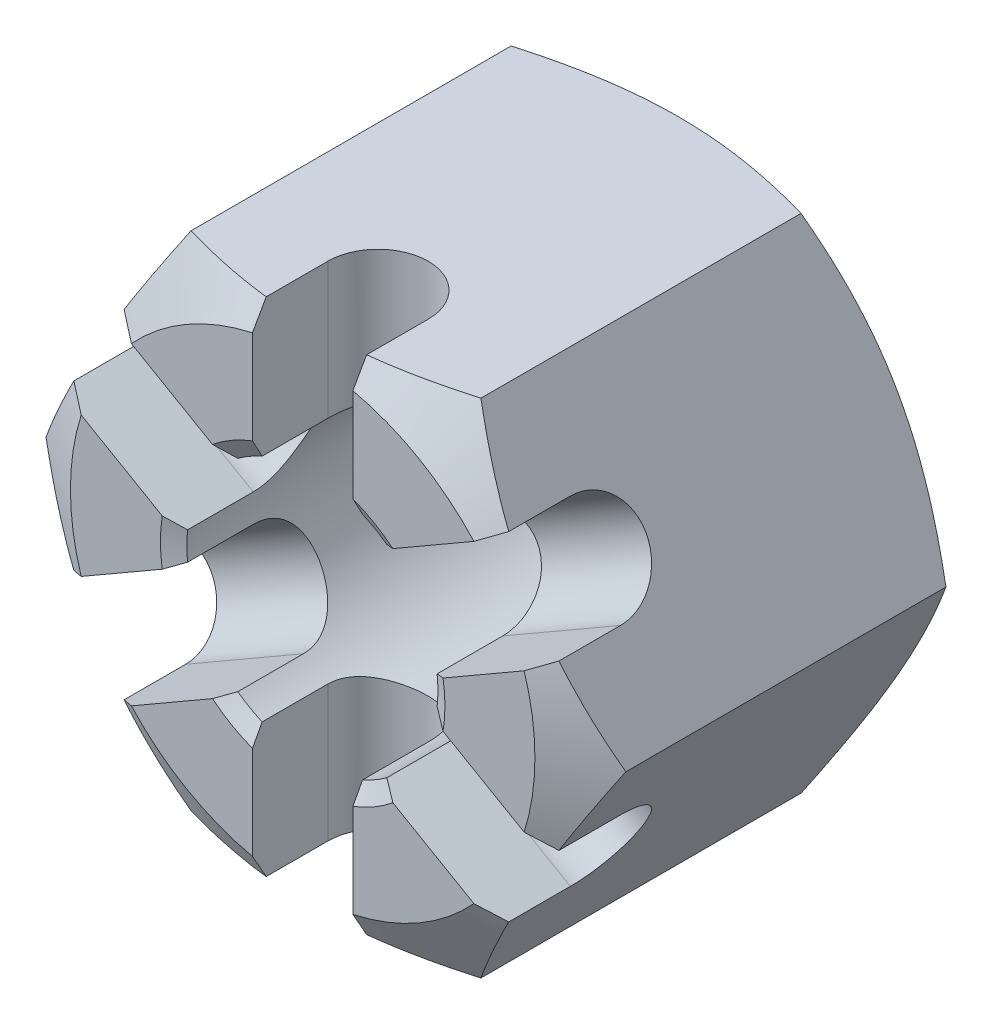
SolidWorks part; units mm, degrees
ref_plane "Front" through (0, 0, 0) normal (0, 0, 1) x (1, 0, 0)
ref_plane "Top" through (0, 0, 0) normal (0, 1, 0) x (1, 0, 0)
ref_plane "Right" through (0, 0, 0) normal (1, 0, 0) x (0, 0, -1)
sketch "Sketch1" plane through (0, 0, 0) normal (0, 0, 1) x (1, 0, 0)
  line L1 (2.8868, -5) -> (5.7735, 0)
  line L2 (5.7735, 0) -> (2.8868, 5)
  line L3 (2.8868, 5) -> (-2.8868, 5)
  line L4 (-2.8868, 5) -> (-5.7735, 0)
  line L5 (-5.7735, 0) -> (-2.8868, -5)
  line L6 (-2.8868, -5) -> (2.8868, -5)
  circle A0 centre (0, 0) radius 5 construction
  circle A1 centre (0, 0) radius 2.5
extrude "BaseNut" add sketch "Sketch1" against normal blind 7.7
cosmetic thread "ThreadCosmetic1" [suppressed] parameters "D"=6
sketch "Sketch2" plane through (0, 0, 0) normal (0, 1, 0) x (1, 0, 0)
  line L0 (-5.7735, 7.7) -> (-4.625, 7.7)
  line L2 (-4.625, 7.7) -> (-5.7735, 7.0369)
  line L3 (-5.7735, 7.0369) -> (-5.7735, 7.7)
  line L4 (0, 3.3759) -> (0, -9.8171) construction
  line L6 (-9.7712, 3.85) -> (9.8853, 3.85) construction
  line L7 (-5.7735, 0.6631) -> (-5.7735, 0)
  line L8 (-4.625, 0) -> (-5.7735, 0.6631)
  line L9 (-5.7735, 0) -> (-4.625, 0)
  dimension "D1" = 30
  dimension "D2" = 3.85
revolve "Double-Chamfer" cut sketch "Sketch2" angle 360 about L4
chamfer "EndChamfer" distance 0.3333 angle 30 2 edges at (2.5, 0, -7.7) (2.5, 0, 0) first distance on face at (2.5, 0, -7.7) first distance on face at (-4.625, 0, 0)
sketch "Sketch3" plane through (0, 0, 0) normal (0, 1, 0) x (1, 0, 0)
  line L0 (0, 4.2201) -> (0, -10.5237) construction
  line L2 (-1, 0) -> (-1, 1.5)
  line L3 (1, 0) -> (1, 1.5)
  line L4 (2.6925, 7.7) -> (-2.6925, 7.7) construction
  arc A0 (-1, 1.5) -> (1, 1.5) centre (0, 1.5) cw
  point P2 (0, 2.5)
  point P3 (0, 7.7)
  dimension "W" = 5.2
  dimension "n" = 2
extrude "Slot" cut sketch "Sketch3" against normal through all and the other way through all
ref_axis "Axis1" through (0, 0, 9.8171) along (0, 0, -1)
pattern_circular "SlotPattern" count 3 over 360 about axis through (0, 0, 9.8171) along (0, 0, -1) of "Slot"
sketch "Sketch4" plane through (0, 0, 0) normal (0, 1, 0) x (1, 0, 0)
  line L0 (0, 9.27) -> (0, 5.1988) construction
  line L1 (2, 7.6167) -> (2.5, 7.6167)
  line L2 (2.5, 7.6167) -> (2.933, 7.3667)
  line L3 (2.933, 7.3667) -> (2.5, 7.1167)
  line L4 (2.5, 7.1167) -> (2, 7.1167)
  line L5 (2, 7.1167) -> (2, 7.6167)
  line L7 (2.5, 7.3667) -> (-2.5, 7.3667) construction
  dimension "D1" = 0.5
  dimension "D2" = 5
revolve "Cut-Revolve10" [suppressed] cut sketch "Sketch4" angle 360 about L0
pattern_linear "LPattern10" [suppressed] count 13 spacing 0.6 along (0, 0, 1) of bodies 105
equation "\"dw@Sketch2\" = \"s@Sketch1\"-0.75"
equation "\"D2@Sketch2\" = \"m@BaseNut\" / 2"
equation "\"D1@EndChamfer\" = \"D@Sketch1\" / 15"
equation "\"D2@Sketch4\" = \"D@Sketch1\""
equation "\"D1@Sketch4\" = (  \"D@ThreadCosmetic1\" - \"D@Sketch1\" )  / 2"
equation "\"D3@LPattern10\" = \"D1@Sketch4\" * 1.2"
equation "\"D1@LPattern10\" =  \"m@BaseNut\"   / \"D3@LPattern10\""
